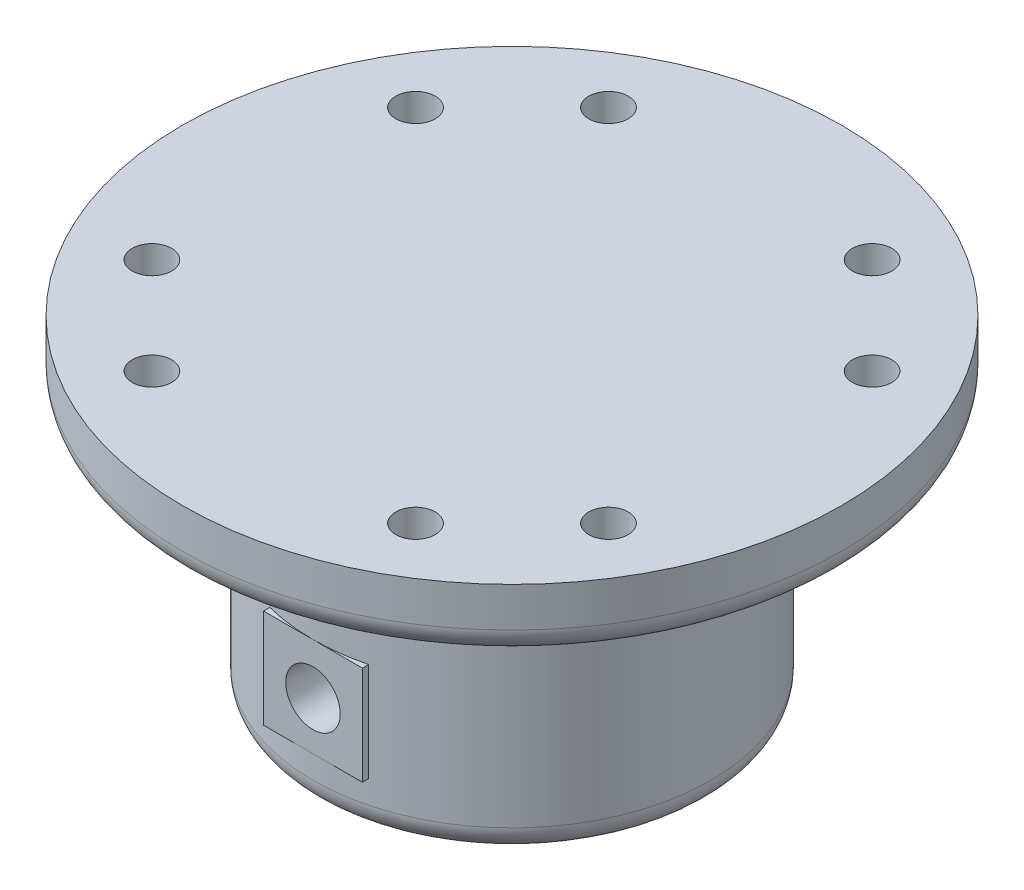
SolidWorks part; units mm, degrees
ref_plane "Front Plane" through (0, 0, 0) normal (0, 0, 1) x (1, 0, 0)
ref_plane "Top Plane" through (0, 0, 0) normal (0, 1, 0) x (1, 0, 0)
ref_plane "Right Plane" through (0, 0, 0) normal (1, 0, 0) x (0, 0, -1)
sketch "Sketch1" plane through (0, 0, 0) normal (0, 1, 0) x (1, 0, 0)
  circle A0 centre (0, 0) radius 31.75 construction
  circle A1 centre (0, 0) radius 19.177 construction
  circle A2 centre (0, 0) radius 12.827 construction
  dimension "D1" = 63.5
  dimension "D2" = 25.654
  dimension "D3" = 6.35
sketch "Sketch6" plane through (0, 0, 0) normal (0, 0, 1) x (1, 0, 0)
  line L0 (0, -18.7832) -> (0, 8.1093) construction
sketch "Sketch2" plane through (0, 0, 0) normal (0, 1, 0) x (1, 0, 0)
  circle A0 centre (0, 0) radius 31.75 construction
  circle A1 centre (0, 0) radius 31.75
extrude "Boss-Extrude1" add sketch "Sketch2" along normal blind 6.35
sketch "Sketch3" plane through (0, 0, 0) normal (0, 1, 0) x (1, 0, 0)
  circle A0 centre (0, 0) radius 19.177 construction
  circle A1 centre (0, 0) radius 19.177
extrude "Boss-Extrude2" add sketch "Sketch3" against normal blind 25.4
sketch "Sketch9" plane through (0, 0, 0) normal (1, 0, 0) x (0, 0, -1)
  line L0 (-19.177, 0) -> (-19.177, -25.4) construction
  line L1 (-19.177, -11.1125) -> (-16.002, -11.1125)
  line L2 (-19.177, -11.1125) -> (-19.177, -20.6375)
  line L3 (-19.177, -20.6375) -> (-16.002, -20.6375)
  line L4 (19.177, -11.1125) -> (19.177, -20.6375)
  line L5 (19.177, -25.4) -> (19.177, 0) construction
  line L6 (16.002, -11.1125) -> (19.177, -11.1125)
  line L8 (-16.002, -11.1125) -> (-16.002, -20.6375)
  line L10 (16.002, -11.1125) -> (16.002, -20.6375)
  line L11 (16.002, -20.6375) -> (19.177, -20.6375)
  point P12 (16.002, -15.875)
  dimension "D1" = 9.525
  dimension "D2" = 15.875
  dimension "D3" = 3.175
  dimension "D4" = 3.175
extrude "Boss-Extrude4" add sketch "Sketch9" along normal mid plane 9.525
sketch "Sketch4" plane through (0, 0, 0) normal (0, 1, 0) x (1, 0, 0)
  circle A0 centre (0, 0) radius 12.827 construction
  circle A1 centre (0, 0) radius 12.827
extrude "Cut-Extrude1" cut sketch "Sketch4" against normal through all
sketch "Sketch5" plane through (0, 0, 0) normal (0, 1, 0) x (1, 0, 0)
  line L0 (0, 0) -> (37.5473, 0) construction
  line L1 (0, 0) -> (21.997, 12.7) construction
  circle A1 centre (21.997, 12.7) radius 1.9
  circle A2 centre (21.997, -12.7) radius 1.9
  dimension "D5" = 3.8
  dimension "D2" = 30
  dimension "D3" = 25.4
extrude "Cut-Extrude2" cut sketch "Sketch5" along normal through all
sketch "Sketch7" plane through (0, 0, 0) normal (0, 0, 1) x (1, 0, 0)
  line L0 (0, -18.7832) -> (0, 8.1093) construction
  circle A0 centre (0, -16.002) radius 2.627
  dimension "D1" = 5.254
  dimension "D2" = 16.002
extrude "Cut-Extrude3" cut sketch "Sketch7" against normal through all both and the other way through all
pattern_circular "CirPattern2" count 4 over 360 about axis through (0, -18.7832, 0) along (0, 1, 0) of "Cut-Extrude2" reverse direction yes
fillet "Fillet1" radius 2.54 5 edges at (0, 0, 19.177) (0, 0, 12.827) (0, 0, 31.75) (0, -25.4, 12.827) (0, -25.4, 19.177)
equation "\"tightTol\" = 0.005in"
equation "\"normTol\"= 0.01in"
equation "\"looseTol\"= 0.02in"
equation "\"D2@Sketch1\"=\"normTol\"+1.000000in"
equation "\"D5@Sketch5\"=3.8mm"
equation "\"D1@Sketch7\"=\"normTol\"+5mm"
equation "\"D2@Sketch7\"=\"tightTol\"+0.625000in"
